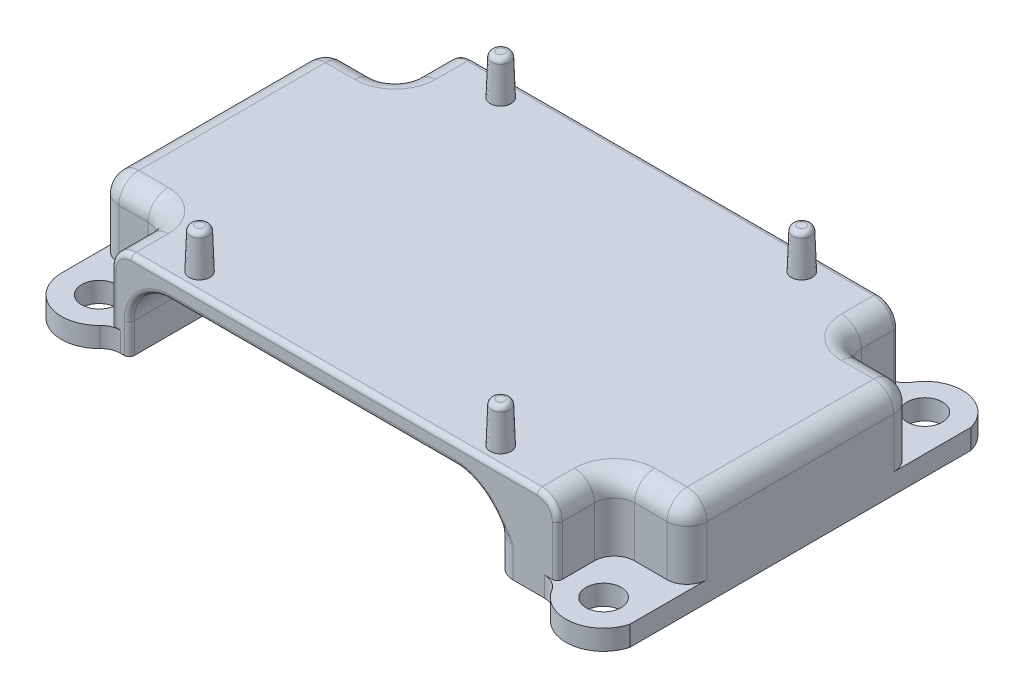
SolidWorks part; units mm, degrees
ref_plane "Front Plane" through (0, 0, 0) normal (0, 0, 1) x (1, 0, 0)
ref_plane "Top Plane" through (0, 0, 0) normal (0, 1, 0) x (1, 0, 0)
ref_plane "Right Plane" through (0, 0, 0) normal (1, 0, 0) x (0, 0, -1)
sketch "Sketch1" plane through (0, 0, 0) normal (0, 1, 0) x (1, 0, 0)
  line L0 (0, 30) -> (0, 0) construction
  line L1 (51.25, 31) -> (51.25, -1) construction
  line L2 (-3.75, 30) -> (-3.75, 0)
  line L3 (-3.1721, 32) -> (5, 32)
  line L4 (-3.1721, 32) -> (-3.1721, -2)
  line L5 (-3.1721, -2) -> (5, -2)
  line L6 (5, 32) -> (5, -2)
  line L7 (54.8642, -2) -> (41.25, -2)
  line L8 (54.8642, -2) -> (54.8642, 32)
  line L9 (54.8642, 32) -> (41.25, 32)
  line L10 (41.25, -2) -> (41.25, 32)
  circle A0 centre (51.25, 31) radius 1.75
  circle A1 centre (51.25, -1) radius 1.75
  circle A2 centre (0, 0) radius 1.75
  circle A3 centre (0, 30) radius 1.75
  circle A4 centre (0, 30) radius 3.75
  circle A5 centre (51.25, 31) radius 3.75
  circle A6 centre (51.25, -1) radius 3.75
  circle A7 centre (0, 0) radius 3.75
  point P16 (0, 15)
  point P17 (51.25, 15)
  dimension "D1" = 3.5
  dimension "D2" = 2
  dimension "D3" = 32
  dimension "D4" = 30
  dimension "D5" = 51.25
  dimension "D6" = 10
  dimension "D7" = 5
  dimension "D8" = 34
  dimension "D9" = 34
extrude "Boss-Extrude1" add sketch "Sketch1" along normal blind 2 contours A7 L5 L6 L3 A4 L4 | L3 A4 A3 | L3 A4 A3 | L5 A7 A2 | A6 L8 A5 L9 L10 L7 | L7 A6 A1 | L7 A6 A1 | L9 A5 A0 | L9 A5 A0 | L5 A7 A2 | L4 A7 | A7 L4 A4 L2 | L4 A4 region at (-3.4667, 0, -15) region at (-3.4049, 0, -30) region at (-3.4049, 0, 0) region at (0, 0, -32.7162) region at (0, 0, -31.91) region at (1.1679, 0, -15) region at (-3.0822, 0, 0) region at (0, 0, 2.7162) region at (51.25, 0, 3.2403) region at (53.7752, 0, 1.9124) region at (47.5973, 0, -15) region at (50.2734, 0, -27.4703) region at (51.25, 0, -33.2403)
sketch "Sketch3" plane through (0, 2, 0) normal (0, 1, 0) x (1, 0, 0)
  line L0 (-3.75, 30) -> (-3.75, 0) construction
  line L1 (3.1721, 32) -> (47.6358, 32)
  line L2 (3.1721, 32) -> (3.1721, -2)
  line L3 (3.1721, -2) -> (47.6358, -2)
  line L4 (47.6358, 32) -> (47.6358, -2)
  line L5 (-3.75, 3.7) -> (54.8642, 3.7)
  line L6 (-3.75, 3.7) -> (-3.75, 26.3)
  line L7 (-3.75, 26.3) -> (54.8642, 26.3)
  line L8 (54.8642, 3.7) -> (54.8642, 26.3)
  line L9 (54.8642, -2) -> (54.8642, 32) construction
  circle A0 centre (0, 30) radius 1.75 construction
  point P14 (-3.75, 17.4374)
  point P15 (-3.75, 52.8046)
  point P16 (-3.75, 15)
  point P17 (-3.75, 15)
  line M14 (-3.75, 30) -> (-3.75, 0)
  dimension "D1" = 3.7
extrude "Boss-Extrude2" add sketch "Sketch3" along normal blind 7 contours L5 L8 L7 L4 | L7 L5 L2 M14 | L3 L4 L1 L2 region at (-0.2889, 2, -15) region at (51.25, 2, -15)
sketch "Sketch4" plane through (0, 0, -32) normal (0, 0, -1) x (-1, 0, 0)
  line L1 (-5, 0) -> (-41.25, 0)
  line L2 (-5, 0) -> (-5, 7)
  line L3 (-5, 7) -> (-41.25, 7)
  line L4 (-41.25, 0) -> (-41.25, 7)
  point P5 (-41.25, 5.9185)
  point P7 (0, 0)
  point P8 (-38.5305, 0)
  point P10 (0, 0)
  dimension "D1" = 7
extrude "Cut-Extrude1" cut sketch "Sketch4" against normal up to next
sketch "Sketch5" plane through (0, 9, 0) normal (0, 1, 0) x (1, 0, 0)
  line L0 (-3.75, 26.3) -> (-3.75, 3.7) construction
  line L3 (40, 0) -> (10, 0)
  line L6 (40, 0) -> (40, 30)
  line L7 (40, 30) -> (10, 30)
  line L8 (10, 0) -> (10, 30)
  line L9 (40, 0) -> (10, 30) construction
  line L10 (40, 30) -> (10, 0) construction
  circle A4 centre (10, 30) radius 0.9
  circle A5 centre (10, 0) radius 0.9
  circle A6 centre (40, 0) radius 0.9
  circle A7 centre (40, 30) radius 0.9
  point P0 (25, 15)
  point P8 (-3.75, 15)
  dimension "D3" = 1.8
  dimension "D1" = 30
  dimension "D2" = 30
  dimension "D4" = 10
extrude "Boss-Extrude3" add sketch "Sketch5" along normal blind 4 contours A4 | A5 | A6 | A7
fillet "Fillet1" radius 2 24 edges at (47.6358, 9, -29.15) (47.6358, 9, -0.85) (3.1721, 9, -29.15) (3.1721, 9, -0.85) (41.25, 3.5, 2) (41.25, 3.5, -32) (47.6358, 1, -32) (51.25, 9, -26.3) (54.8642, 5.5, -3.7) (54.8642, 5.5, -26.3) (54.8642, 9, -15) (47.6358, 1, 2) (3.1721, 1, 2) (3.1721, 1, -32) (51.25, 9, -3.7) (-0.2889, 9, -26.3) (-0.2889, 9, -3.7) (-3.75, 9, -15) (-3.75, 5.5, -26.3) (-3.75, 5.5, -3.7) (3.1721, 5.5, -26.3) (47.6358, 5.5, -26.3) (47.6358, 5.5, -3.7) (3.1721, 5.5, -3.7)
fillet "Fillet2" radius 4 4 edges at (41.8358, 7, 1.4142) (41.8358, 7, -31.4142) (41.25, 7, -15) (5, 7, -15)
fillet "Fillet3" radius 0.5 18 edges at (3.1721, 4.5, 2) (3.7579, 8.4142, 2) (47.6358, 4.5, 2) (47.05, 8.4142, 2) (3.1721, 4.5, -32) (3.7579, 8.4142, -32) (47.6358, 4.5, -32) (47.05, 8.4142, -32) (40.5096, 6.0334, -32) (23.2966, 7, -32) (6.1716, 5.8284, -32) (40.5096, 6.0334, 2) (23.2966, 7, 2) (6.1716, 5.8284, 2) (25.404, 9, 2) (25.404, 9, -32) (5, 1.5, -32) (5, 1.5, 2)
draft "Draft4" type of draft neutral plane draft angle 2 faces to draft 4 face at (10, 13, 0.9) face at (40, 13, 0.9) face at (40, 13, -29.1) face at (10, 13, -29.1) neutral plane through (10, 13, -30) neutral plane normal (0, 1, 0) parameters "D1"=2
fillet "Fillet4" radius 0.5 4 edges at (40, 13, -29.1) (40, 13, 0.9) (10, 13, 0.9) (10, 13, -29.1)
